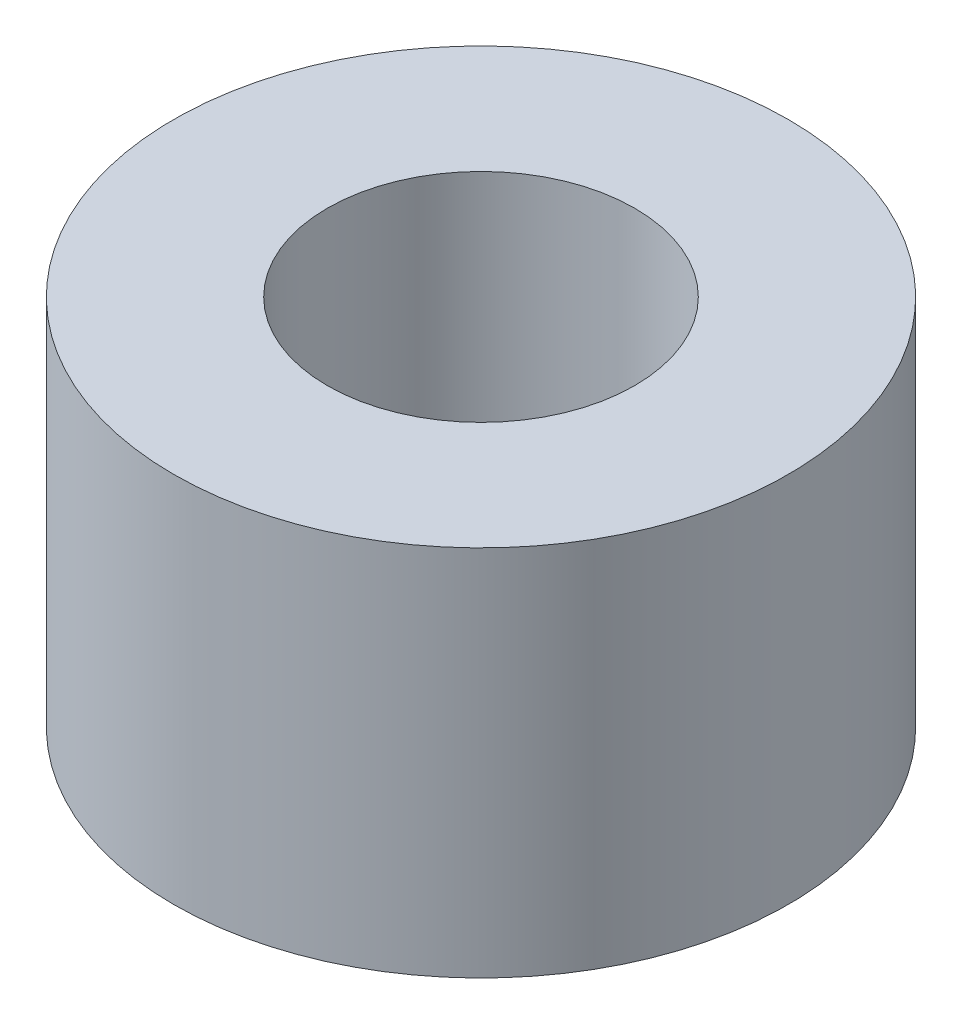
SolidWorks part; units mm, degrees
material "Brass"
ref_plane "Front Plane" through (0, 0, 0) normal (0, 0, 1) x (1, 0, 0)
ref_plane "Top Plane" through (0, 0, 0) normal (0, 1, 0) x (1, 0, 0)
ref_plane "Right Plane" through (0, 0, 0) normal (1, 0, 0) x (0, 0, -1)
ref_axis "X Axis" through (-88.99, 0, 0) along (1, 0, 0)
ref_axis "Y Axis" through (0, 55, 0) along (0, -1, 0)
ref_axis "Z Axis" through (0, 0, -88.99) along (0, 0, 1)
sketch "Sketch1" plane through (0, 0, 0) normal (0, 0, 1) x (1, 0, 0)
  line L0 (0, 0) -> (0, -0.8542) construction
  line L1 (0, 0) -> (2.5, 0)
  line L2 (0, 0) -> (0, 3.03)
  line L3 (0, 3.03) -> (2.5, 3.03)
  line L4 (2.5, 0) -> (2.5, 3.03)
  line L5 (1.25, 3.03) -> (1.25, 0) construction
  line L6 (0, 1.515) -> (2.5, 1.515) construction
  point P0 (1.25, 1.515)
  dimension "D1" = 5
  dimension "D2" = 3.03
revolve "Revolve1" add sketch "Sketch1" angle 360 about L0
hole_wizard "M3x0.5 Tapped Hole1" positions "Sketch2" profile "Sketch3" tap size "M3x0.5" standard "ANSI Metric"
sketch "Sketch2" plane through (0, 3.03, 0) normal (0, 1, 0) x (1, 0, 0)
  point P0 (0, 0)
sketch "Sketch3" plane through (0, 3.03, 0) normal (1, 0, 0) x (0, 0, 1)
  line L0 (0, 0) -> (0, 9.2511)
  line L1 (0, 9.2511) -> (1.25, 8.5)
  line L2 (1.25, 8.5) -> (1.25, 0)
  line L5 (1.25, 0) -> (0, 0)
  line L10 (0, 9.2511) -> (-1.25, 8.5) construction
  line L11 (0, -6.35) -> (0, 107.95) construction
  dimension "Tap Drill Dia." = 2.5
  dimension "Tap Drill Depth" = 8.5
  dimension "Drill Angle" = 118
cosmetic thread "Hole Thread1" parameters "D1"=6, "D2"=3
